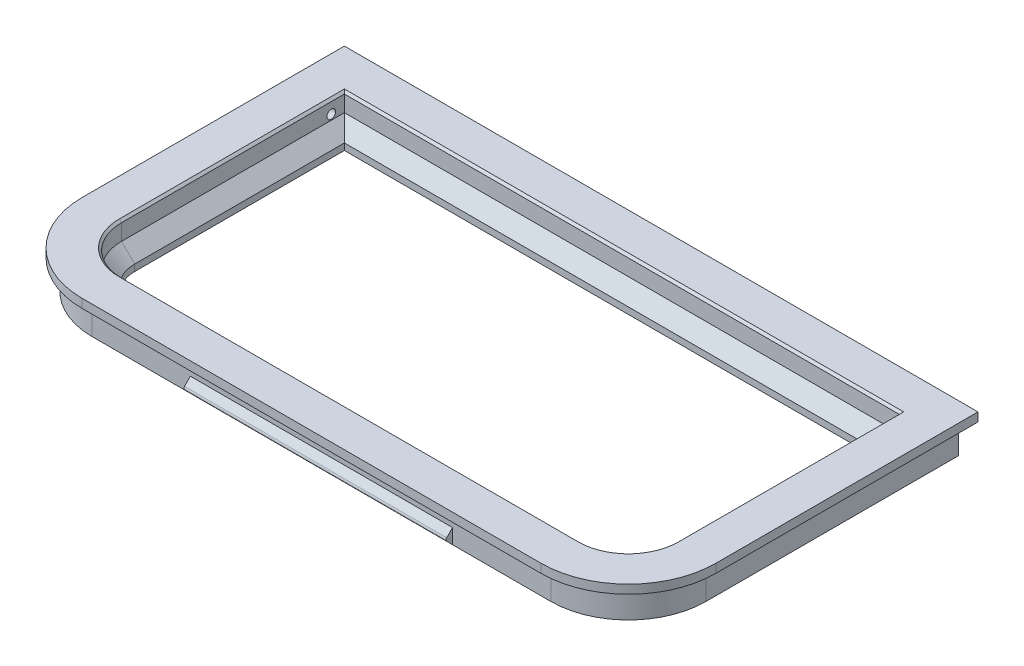
SolidWorks part; units mm, degrees
material "ПК/АБС"
ref_plane "Спереди" through (0, 0, 0) normal (0, 0, 1) x (1, 0, 0)
ref_plane "Сверху" through (0, 0, 0) normal (0, 1, 0) x (1, 0, 0)
ref_plane "Справа" through (0, 0, 0) normal (1, 0, 0) x (0, 0, -1)
sketch "Эскиз1" plane through (0, 0, 0) normal (0, 1, 0) x (1, 0, 0)
  line L1 (-72.5, -40) -> (72.5, -40)
  line L2 (-72.5, -40) -> (-72.5, 40)
  line L3 (-72.5, 40) -> (72.5, 40)
  line L4 (72.5, -40) -> (72.5, 40)
  line L5 (-72.5, -40) -> (72.5, 40) construction
  line L6 (-72.5, 40) -> (72.5, -40) construction
  point P0 (0, 0)
  dimension "D1" = 145
  dimension "D2" = 80
extrude "Бобышка-Вытянуть1" add sketch "Эскиз1" along normal blind 2
fillet "Скругление1" radius 20 2 edges at (-72.5, 1, 40) (72.5, 1, 40)
sketch "Эскиз2" plane through (0, 2, 0) normal (0, 1, 0) x (1, 0, 0)
  line L8 (-63.5, 31) -> (-63.5, -20)
  line L9 (-52.5, -31) -> (52.5, -31)
  line L10 (63.5, -20) -> (63.5, 31)
  line L11 (63.5, 31) -> (-63.5, 31)
  line L12 (-63.5, 31) -> (-63.5, -20)
  line L13 (-52.5, -31) -> (52.5, -31)
  line L14 (63.5, -20) -> (63.5, 31)
  line L15 (63.5, 31) -> (-63.5, 31)
  arc A4 (-63.5, -20) -> (-52.5, -31) centre (-52.5, -20) ccw
  arc A5 (52.5, -31) -> (63.5, -20) centre (52.5, -20) ccw
  arc A6 (-63.5, -20) -> (-52.5, -31) centre (-52.5, -20) ccw
  arc A7 (52.5, -31) -> (63.5, -20) centre (52.5, -20) ccw
  dimension "D1" = 9
extrude "Вырез-Вытянуть1" cut sketch "Эскиз2" against normal blind 2
sketch "Эскиз3" plane through (0, 0, 0) normal (0, -1, 0) x (1, 0, 0)
  line L15 (-63.5, -31) -> (-63.5, 20) construction
  line L16 (63.5, -31) -> (-63.5, -31) construction
  line L17 (63.5, 20) -> (63.5, -31) construction
  line L18 (-52.5, 31) -> (52.5, 31) construction
  line L19 (70.25, -37.75) -> (70.25, 20)
  line L20 (-70.25, -37.75) -> (70.25, -37.75)
  line L21 (-70.25, 20) -> (-70.25, -37.75)
  line L22 (52.5, 37.75) -> (-52.5, 37.75)
  line L23 (70.25, -37.75) -> (70.25, 20)
  line L24 (-70.25, -37.75) -> (70.25, -37.75)
  line L25 (-70.25, 20) -> (-70.25, -37.75)
  line L26 (52.5, 37.75) -> (-52.5, 37.75)
  line L27 (-63.5, -31) -> (-63.5, 20)
  line L28 (63.5, -31) -> (-63.5, -31)
  line L29 (63.5, 20) -> (63.5, -31)
  line L30 (-52.5, 31) -> (52.5, 31)
  arc A6 (-52.5, 31) -> (-63.5, 20) centre (-52.5, 20) ccw construction
  arc A7 (63.5, 20) -> (52.5, 31) centre (52.5, 20) ccw construction
  arc A8 (70.25, 20) -> (52.5, 37.75) centre (52.5, 20) ccw
  arc A9 (-52.5, 37.75) -> (-70.25, 20) centre (-52.5, 20) ccw
  arc A10 (70.25, 20) -> (52.5, 37.75) centre (52.5, 20) ccw
  arc A11 (-52.5, 37.75) -> (-70.25, 20) centre (-52.5, 20) ccw
  arc A12 (-52.5, 31) -> (-63.5, 20) centre (-52.5, 20) ccw
  arc A13 (63.5, 20) -> (52.5, 31) centre (52.5, 20) ccw
  dimension "D1" = 6.75
extrude "Бобышка-Вытянуть2" add sketch "Эскиз3" along normal blind 2
sketch "Эскиз5" plane through (0, 0, 0) normal (1, 0, 0) x (0, 0, -1)
  line L0 (-20, 0) -> (40, 0) construction
  line L7 (37.75, -2) -> (31, -2)
  line L9 (31, -2) -> (31, -6.7)
  line L10 (31, -6.7) -> (37.75, -6.7)
  line L11 (37.75, -6.7) -> (39.45, -5)
  line L12 (39.45, -5) -> (37.75, -3.3)
  line L13 (37.75, -3.3) -> (37.75, -2)
  line L14 (31, -2) -> (31, 2) construction
  line L15 (31, -2) -> (31, 2) construction
  line L16 (-31, -2) -> (-31, 2) construction
  line L17 (-31, -2) -> (-31, 2) construction
  line L18 (-31, -2) -> (-31, -6.7)
  line L19 (-31, -6.7) -> (-37.75, -6.7)
  line L20 (-37.75, -6.7) -> (-39.45, -5)
  line L21 (-39.45, -5) -> (-37.75, -3.3)
  line L22 (-37.75, -3.3) -> (-37.75, -2)
  line L23 (-37.75, -2) -> (-31, -2)
  point P8 (-37.75, -5.8891)
  dimension "D1" = 5
  dimension "D2" = 1.7
  dimension "D4" = 1.7
extrude "Бобышка-Вытянуть4" add sketch "Эскиз5" along normal mid plane 15
sketch "Эскиз6" plane through (0, 0, 0) normal (1, 0, 0) x (0, 0, -1)
  line L6 (-39.45, -5) -> (-37.75, -6.7)
  line L7 (-37.75, -6.7) -> (-31, -6.7)
  line L8 (-31, -6.7) -> (-31, -2)
  line L9 (-31, -2) -> (-37.75, -2)
  line L10 (-37.75, -2) -> (-37.75, -3.3)
  line L11 (-37.75, -3.3) -> (-39.45, -5)
  line L12 (-39.45, -5) -> (-37.75, -6.7)
  line L13 (-37.75, -6.7) -> (-31, -6.7)
  line L14 (-31, -6.7) -> (-31, -2)
  line L15 (-31, -2) -> (-37.75, -2)
  line L16 (-37.75, -2) -> (-37.75, -3.3)
  line L17 (-37.75, -3.3) -> (-39.45, -5)
  dimension "D1" = 0
extrude "Бобышка-Вытянуть5" add sketch "Эскиз6" along normal mid plane 60
fillet "Скругление2" radius 0.5 2 edges at (0, -5, 39.45) (0, -5, -39.45)
sketch "Эскиз7" plane through (0, -2, 0) normal (0, -1, 0) x (1, 0, 0)
  line L8 (-52.5, 31) -> (-30, 31)
  line L9 (-30, 31) -> (-30, 37.75)
  line L10 (-30, 37.75) -> (-52.5, 37.75)
  line L11 (-70.25, 20) -> (-70.25, -37.75)
  line L12 (-70.25, -37.75) -> (-7.5, -37.75)
  line L13 (-7.5, -37.75) -> (-7.5, -31)
  line L14 (-7.5, -31) -> (-63.5, -31)
  line L15 (-63.5, -31) -> (-63.5, 20)
  line L16 (-52.5, 31) -> (-30, 31)
  line L17 (-30, 31) -> (-30, 37.75)
  line L18 (-30, 37.75) -> (-52.5, 37.75)
  line L19 (-70.25, 20) -> (-70.25, -37.75)
  line L20 (-70.25, -37.75) -> (-7.5, -37.75)
  line L21 (-7.5, -37.75) -> (-7.5, -31)
  line L22 (-7.5, -31) -> (-63.5, -31)
  line L23 (-63.5, -31) -> (-63.5, 20)
  line L24 (30, 37.75) -> (30, 31)
  line L25 (30, 31) -> (52.5, 31)
  line L26 (63.5, 20) -> (63.5, -31)
  line L27 (63.5, -31) -> (7.5, -31)
  line L28 (7.5, -31) -> (7.5, -37.75)
  line L29 (7.5, -37.75) -> (70.25, -37.75)
  line L30 (70.25, -37.75) -> (70.25, 20)
  line L31 (52.5, 37.75) -> (30, 37.75)
  line L32 (30, 37.75) -> (30, 31)
  line L33 (30, 31) -> (52.5, 31)
  line L34 (63.5, 20) -> (63.5, -31)
  line L35 (63.5, -31) -> (7.5, -31)
  line L36 (7.5, -31) -> (7.5, -37.75)
  line L37 (7.5, -37.75) -> (70.25, -37.75)
  line L38 (70.25, -37.75) -> (70.25, 20)
  line L39 (52.5, 37.75) -> (30, 37.75)
  arc A2 (-52.5, 37.75) -> (-70.25, 20) centre (-52.5, 20) ccw
  arc A3 (-52.5, 31) -> (-63.5, 20) centre (-52.5, 20) ccw
  arc A4 (-52.5, 37.75) -> (-70.25, 20) centre (-52.5, 20) ccw
  arc A5 (-52.5, 31) -> (-63.5, 20) centre (-52.5, 20) ccw
  arc A6 (63.5, 20) -> (52.5, 31) centre (52.5, 20) ccw
  arc A7 (70.25, 20) -> (52.5, 37.75) centre (52.5, 20) ccw
  arc A8 (63.5, 20) -> (52.5, 31) centre (52.5, 20) ccw
  arc A9 (70.25, 20) -> (52.5, 37.75) centre (52.5, 20) ccw
  dimension "D1" = 0
  dimension "D2" = 0
extrude "Бобышка-Вытянуть6" add sketch "Эскиз7" along normal up to surface (4.7 mm away) up to face at (0, -6.7, 34.375)
sketch "Эскиз10" plane through (0, -6.7, 0) normal (0, -1, 0) x (1, 0, 0)
  line L14 (-63.5, 20) -> (-63.5, -31) construction
  line L15 (63.5, -31) -> (-63.5, -31) construction
  line L16 (63.5, -31) -> (63.5, 20) construction
  line L17 (52.5, 31) -> (-52.5, 31) construction
  line L18 (60.5, -28) -> (60.5, 20)
  line L19 (-60.5, -28) -> (60.5, -28)
  line L20 (-60.5, 20) -> (-60.5, -28)
  line L21 (52.5, 28) -> (-52.5, 28)
  line L22 (60.5, -28) -> (60.5, 20)
  line L23 (-60.5, -28) -> (60.5, -28)
  line L24 (-60.5, 20) -> (-60.5, -28)
  line L25 (52.5, 28) -> (-52.5, 28)
  line L26 (-63.5, 20) -> (-63.5, -31)
  line L27 (63.5, -31) -> (-63.5, -31)
  line L28 (63.5, -31) -> (63.5, 20)
  line L29 (52.5, 31) -> (-52.5, 31)
  arc A7 (-52.5, 31) -> (-63.5, 20) centre (-52.5, 20) ccw construction
  arc A8 (63.5, 20) -> (52.5, 31) centre (52.5, 20) ccw construction
  arc A9 (60.5, 20) -> (52.5, 28) centre (52.5, 20) ccw
  arc A10 (-52.5, 28) -> (-60.5, 20) centre (-52.5, 20) ccw
  arc A11 (60.5, 20) -> (52.5, 28) centre (52.5, 20) ccw
  arc A12 (-52.5, 28) -> (-60.5, 20) centre (-52.5, 20) ccw
  arc A13 (-52.5, 31) -> (-63.5, 20) centre (-52.5, 20) ccw
  arc A14 (63.5, 20) -> (52.5, 31) centre (52.5, 20) ccw
  dimension "D1" = 3
extrude "Бобышка-Вытянуть9" add sketch "Эскиз10" against normal blind 1.5
chamfer "Фаска2" distance 3 angle 45 6 edges at (0, -5.2, -31) (63.5, -5.2, -5.5) (-63.5, -5.2, -5.5) (60.2782, -5.2, 27.7782) (-60.2782, -5.2, 27.7782) (0, -5.2, 31)
sketch "Эскиз11" plane through (70.25, 0, 0) normal (1, 0, 0) x (0, 0, -1)
  line L0 (40, 2) -> (40, 0) construction
  line L1 (-20, 2) -> (40, 2) construction
  circle A0 centre (28, -1) radius 1
  dimension "D1" = 2
  dimension "D2" = 12
  dimension "D3" = 3
extrude "Вырез-Вытянуть2" cut sketch "Эскиз11" against normal through all
chamfer "Фаска3" distance 0.5 angle 45 6 edges at (63.5, 2, -5.5) (60.2782, 2, 27.7782) (0, 2, 31) (-60.2782, 2, 27.7782) (-63.5, 2, -5.5) (0, 2, -31)
